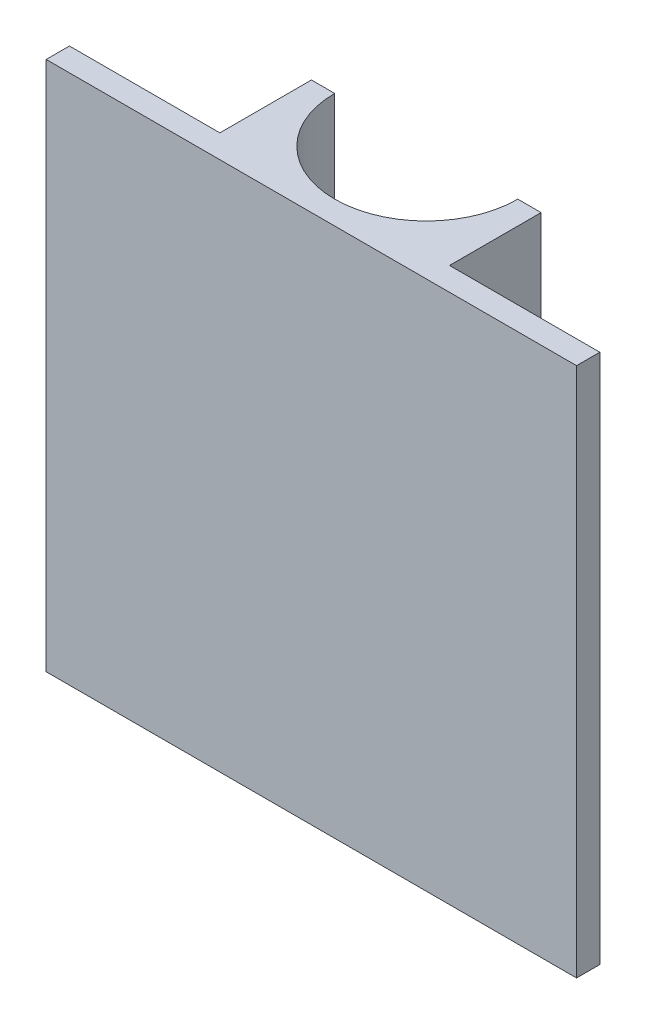
SolidWorks part; units mm, degrees
ref_plane "Front Plane" through (0, 0, 0) normal (0, 0, 1) x (1, 0, 0)
ref_plane "Top Plane" through (0, 0, 0) normal (0, 1, 0) x (1, 0, 0)
ref_plane "Right Plane" through (0, 0, 0) normal (1, 0, 0) x (0, 0, -1)
sketch "Sketch1" plane through (0, 0, 0) normal (0, 1, 0) x (1, 0, 0)
  line L0 (-5.6717, 30.1982) -> (-5.9717, 30.1982)
  line L1 (-29.6816, 17.6982) -> (42.7191, 17.6982)
  line L2 (-29.6816, 17.6982) -> (-29.6816, 14.5232)
  line L3 (-29.6816, 14.5232) -> (42.7191, 14.5232)
  line L4 (42.7191, 17.6982) -> (42.7191, 14.5232)
  line L5 (19.0283, 30.1982) -> (18.7283, 30.1982)
  line L6 (22.2033, 30.1982) -> (-9.1467, 30.1982)
  line L7 (22.2033, 30.1982) -> (22.2033, 17.6982)
  line L8 (22.2033, 17.6982) -> (-9.1467, 17.6982)
  line L9 (-9.1467, 30.1982) -> (-9.1467, 17.6982)
  arc A0 (-5.9717, 30.1982) -> (19.0283, 30.1982) centre (6.5283, 30.1982) ccw
  arc A1 (-5.6717, 30.1982) -> (18.7283, 30.1982) centre (6.5283, 30.1982) ccw
  point P10 (-29.6816, 16.1107)
  point P11 (42.7191, 16.1107)
  dimension "D4" = 12.5
  dimension "D1" = 0
  dimension "D2" = 20.5349
  dimension "D3" = 20.5157
  dimension "D5" = 15.675
extrude "Boss-Extrude4" add sketch "Sketch1" along normal blind 51.39 contours L4 L1 L8 L2 L3 | A0 L8 L7 L6 | A0 L6 L9 L1 | A0 L5 A1 L0 region at (-5.5535, 0, -22.3646) region at (6.5187, 0, -16.1107) region at (18.6101, 0, -22.3646)
extrude "Boss-Extrude5" add sketch "Sketch1<9>" along normal blind 72.39 contours L4 L1 L8 L2 L3 | A0 L8 L7 L6 | A0 L6 L9 L1 region at (-5.5535, 0, -22.3646) region at (6.5187, 0, -16.1107) region at (18.6101, 0, -22.3646)
sketch "Sketch1<9>" plane through (0, 0, 0) normal (0, 1, 0) x (1, 0, 0) same geometry as "Sketch1"
